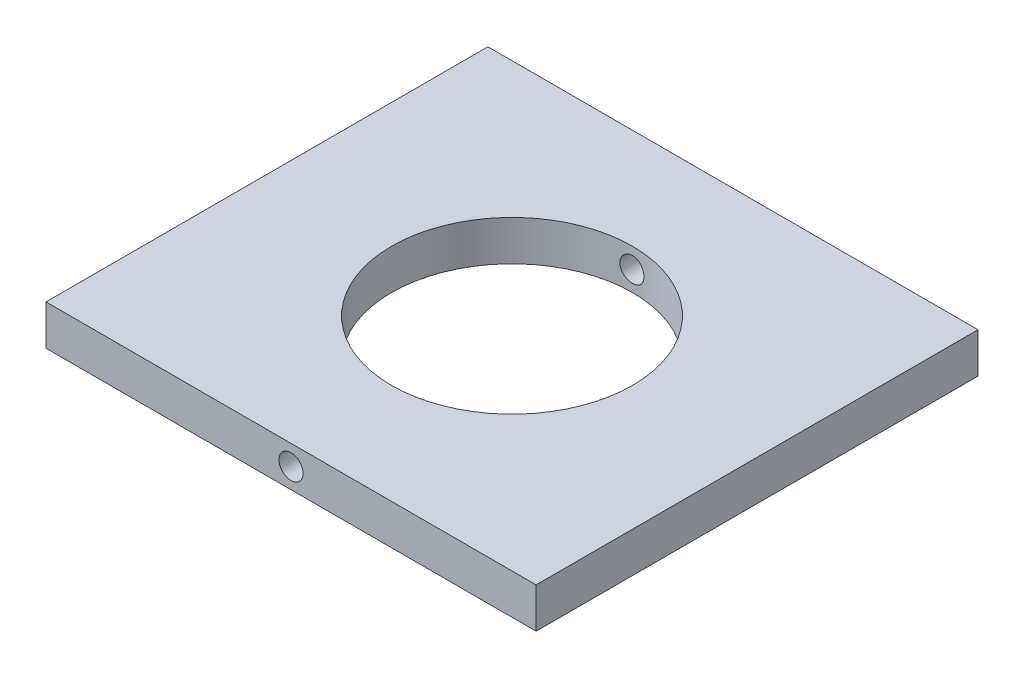
SolidWorks part; units mm, degrees
ref_plane "Plan de face" through (0, 0, 0) normal (0, 0, 1) x (1, 0, 0)
ref_plane "Plan de dessus" through (0, 0, 0) normal (0, 1, 0) x (1, 0, 0)
ref_plane "Plan de droite" through (0, 0, 0) normal (1, 0, 0) x (0, 0, -1)
sketch "Esquisse1" plane through (0, 0, 0) normal (0, 0, 1) x (1, 0, 0)
  line L0 (-8.5, -47.5) -> (52.5, -47.5) construction
  line L5 (-8.5, -45) -> (52.5, -45)
  line L6 (-8.5, -45) -> (-8.5, -50)
  line L7 (-8.5, -50) -> (52.5, -50)
  line L8 (52.5, -45) -> (52.5, -50)
  line L9 (22, -45) -> (22, -50) construction
  dimension "D1" = 5
  dimension "D2" = 61
extrude "Boss.-Extru.1" add sketch "Esquisse1" along normal blind 55 contours L5 | L7 L8 L5 L6
sketch "Esquisse2" plane through (0, -45, 0) normal (0, 1, 0) x (-1, 0, 0)
  line L0 (8.5, 55) -> (-52.5, 55) construction
  line L7 (-52.5, 55) -> (-52.5, 0) construction
  circle A0 centre (-22, 27.5) radius 15
  dimension "D10" = 30.5
  dimension "D11" = 27.5
extrude "Enlèv. mat.-Extru.1" cut sketch "Esquisse2" against normal through all
sketch "Esquisse5" plane through (0, 0, 55) normal (0, 0, 1) x (1, 0, 0)
  line L0 (-8.5, -45) -> (52.5, -45) construction
  line L1 (-8.5, -45) -> (-8.5, -50) construction
  circle A0 centre (22, -47.5) radius 1.5
  dimension "D1" = 2.5
  dimension "D2" = 30.5
extrude "Enlèv. mat.-Extru.4" cut sketch "Esquisse5" against normal through all
